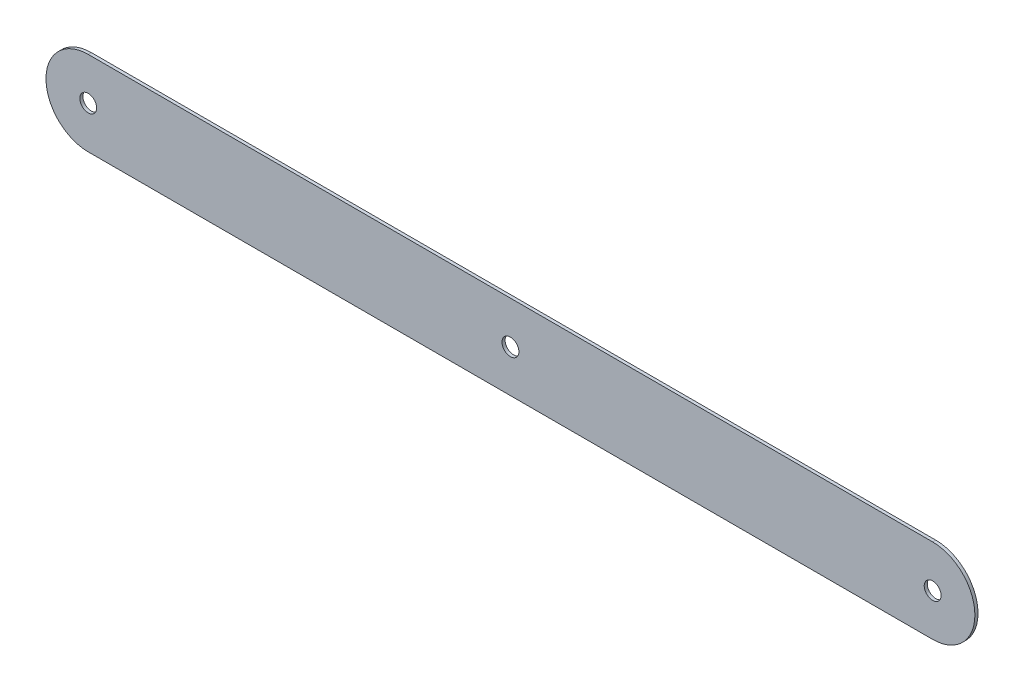
SolidWorks part; units mm, degrees
ref_plane "Front Plane" through (0, 0, 0) normal (0, 0, 1) x (1, 0, 0)
ref_plane "Top Plane" through (0, 0, 0) normal (0, 1, 0) x (1, 0, 0)
ref_plane "Right Plane" through (0, 0, 0) normal (1, 0, 0) x (0, 0, -1)
sketch "Sketch1" plane through (0, 0, 0) normal (0, 0, 1) x (1, 0, 0)
  line L0 (-28.3445, 0) -> (171.6555, 0) construction
  line L1 (-28.3445, 10) -> (171.6555, 10)
  line L2 (-28.3445, -10) -> (171.6555, -10)
  arc A0 (-28.3445, 10) -> (-28.3445, -10) centre (-28.3445, 0) ccw
  arc A1 (171.6555, -10) -> (171.6555, 10) centre (171.6555, 0) ccw
  circle A2 centre (-28.3445, 0) radius 2
  circle A3 centre (171.6555, 0) radius 2
  circle A4 centre (71.6555, 0) radius 2
  point P3 (71.6555, 0)
  dimension "D3" = 4
  dimension "D4" = 4
  dimension "D5" = 4
  dimension "D1" = 200
  dimension "D2" = 20
base flange "Base-Flange1" sketch "Sketch1" thickness 0.7366 reverse thickness direction no parameters "D1"=0.7366
sketch "Bend-Lines1" plane through (0, 0, 0) normal (0, 1, 0) x (1, 0, 0)
sketch "Bounding-Box1" plane through (0, 0, 0) normal (0, 1, 0) x (1, 0, 0)
sheet metal parameters "Sheet-Metal1" thickness 0.7366 parameters "D1"=0.7366
flat pattern "Flat-Pattern1" [suppressed]
sketch "Bend-Lines2" plane through (0, 0, 0) normal (0, 1, 0) x (1, 0, 0)
sketch "Bounding-Box2" [suppressed] plane through (0, 0, 0) normal (0, 1, 0) x (1, 0, 0)
